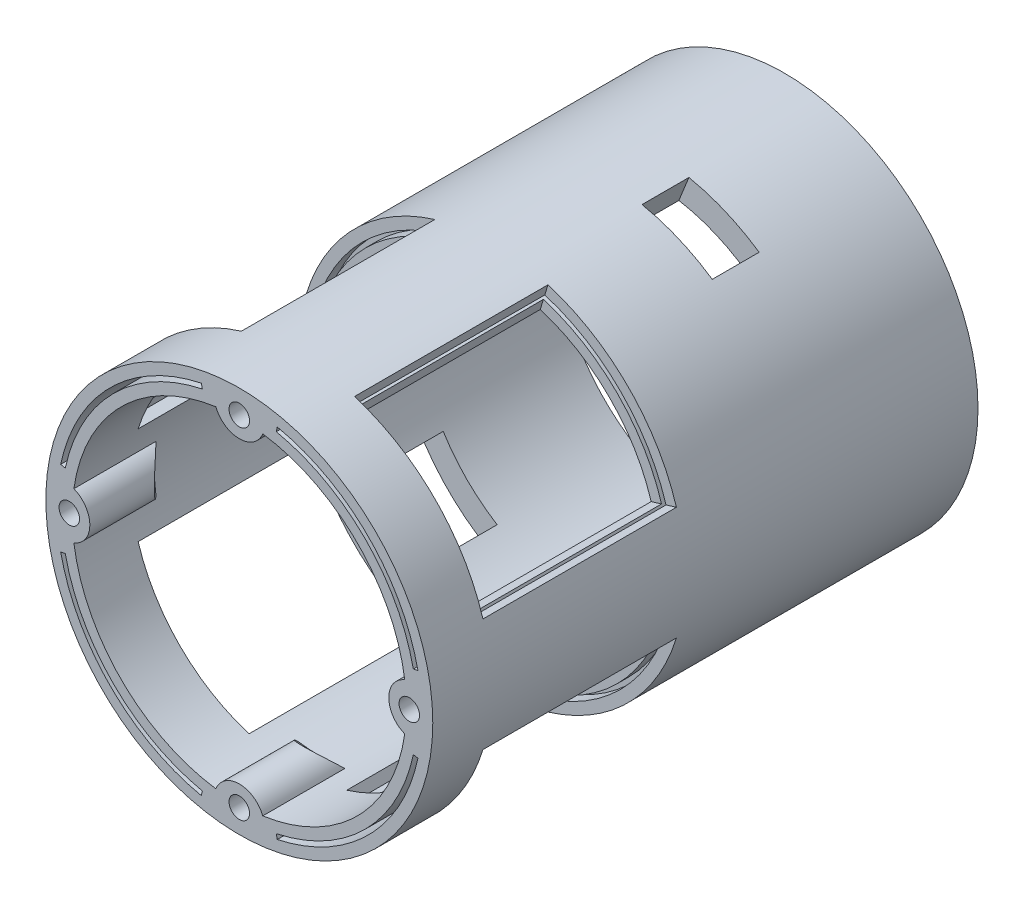
SolidWorks part; units mm, degrees
material "PEI"
ref_plane "Alzado" through (0, 0, 0) normal (0, 0, 1) x (1, 0, 0)
ref_plane "Planta" through (0, 0, 0) normal (0, 1, 0) x (1, 0, 0)
ref_plane "Vista lateral" through (0, 0, 0) normal (1, 0, 0) x (0, 0, -1)
sketch "Croquis1" plane through (0, 0, 0) normal (0, 0, 1) x (1, 0, 0)
  circle A0 centre (0, 0) radius 33
  circle A1 centre (0, 0) radius 28.5
  dimension "D1" = 66
  dimension "D2" = 4.5
extrude "Boss-Extrude1" add sketch "Croquis1" along normal blind 93
sketch "Croquis2" plane through (0, 0, 93) normal (0, 0, 1) x (1, 0, 0)
  line L0 (0, 0) -> (-6.4764, -30.4693) construction
  line L1 (0, 0) -> (-30.4693, -6.4764) construction
  line L2 (0, 0) -> (0, -30.5) construction
  line L3 (0, 0) -> (-30.5, 0) construction
  line L4 (-30.4693, -6.4764) -> (-29.6868, -6.3101)
  line L5 (-6.4764, -30.4693) -> (-6.3101, -29.6868)
  line L6 (-30.4693, 6.4764) -> (-29.6868, 6.3101)
  line L7 (-6.4764, 30.4693) -> (-6.3101, 29.6868)
  line L8 (6.4764, 30.4693) -> (6.3101, 29.6868)
  line L9 (30.4693, 6.4764) -> (29.6868, 6.3101)
  line L10 (30.4693, -6.4764) -> (29.6868, -6.3101)
  line L11 (6.4764, -30.4693) -> (6.3101, -29.6868)
  circle A0 centre (0, 0) radius 30.35 construction
  circle A1 centre (0, 0) radius 31.15 construction
  circle A2 centre (0, 0) radius 33 construction
  circle A3 centre (0, 0) radius 30.75 construction
  arc A4 (-6.4764, -30.4693) -> (-30.4693, -6.4764) centre (0, 0) cw
  arc A5 (-6.3101, -29.6868) -> (-29.6868, -6.3101) centre (0, 0) cw
  arc A6 (-30.4693, 6.4764) -> (-6.4764, 30.4693) centre (0, 0) cw
  arc A7 (-29.6868, 6.3101) -> (-6.3101, 29.6868) centre (0, 0) cw
  arc A8 (6.4764, 30.4693) -> (30.4693, 6.4764) centre (0, 0) cw
  arc A9 (6.3101, 29.6868) -> (29.6868, 6.3101) centre (0, 0) cw
  arc A10 (30.4693, -6.4764) -> (6.4764, -30.4693) centre (0, 0) cw
  arc A11 (29.6868, -6.3101) -> (6.3101, -29.6868) centre (0, 0) cw
  circle A12 centre (0, 0) radius 28.5 construction
  point P4 (-6.3933, -30.078)
  point P32 (0, 0)
  dimension "D3" = 12
  dimension "D4" = 12
  dimension "D1" = 0.8
  dimension "D2" = 4.5
  dimension "D6" = 2.25
  dimension "D5" = 4
extrude "Cortar-Extruir1" cut sketch "Croquis2" against normal blind 45
ref_axis "Eje1" through (0, 0, 93) along (0, 0, -1)
ref_plane "Plano2" through (0, 0, 0) normal (0.9563, -0.2924, 0) x (0, 0, -1)
sketch "Croquis4" plane through (0, 0, 0) normal (0.9563, -0.2924, 0) x (0, 0, -1)
  line L0 (-83, 33) -> (-83, 28.266)
  line L1 (0, 33) -> (-93, 33) construction
  line L2 (-83, 28.266) -> (-50, 28.266)
  line L4 (-50, 33) -> (-83, 33)
  line L5 (-97, 29) -> (-42, 29) construction
  line L6 (-93, 33) -> (-93, -33) construction
  line L14 (-50, 28.266) -> (-50, 33)
  point P10 (-83, 28.1943)
  point P11 (-49.9679, 28.266)
  dimension "D1" = 4.734
  dimension "D6" = 10
revolve "Cortar-Revolución2" cut sketch "Croquis4" angle 56 about axis through (0, 0, 93) along (0, 0, -1)
pattern_circular "MatrizC2" count 4 over 360 about axis through (0, 0, 93) along (0, 0, -1) of "Cortar-Revolución2"
sketch "Sketch8" plane through (0, 0, 0) normal (0, 0, -1) x (-1, 0, 0)
  arc A0 (-4, -28.2179) -> (4, -28.2179) centre (0, 0) ccw
  circle A1 centre (0, 0) radius 28.5 construction
  arc A2 (-4, -28.2179) -> (4, -28.2179) centre (0, -29.7959) cw
  arc A3 (-28.2179, 4) -> (-28.2179, -4) centre (0, 0) ccw
  arc A4 (-28.2179, 4) -> (-28.2179, -4) centre (-29.7959, 0) cw
  arc A5 (4, 28.2179) -> (-4, 28.2179) centre (0, 0) ccw
  arc A6 (4, 28.2179) -> (-4, 28.2179) centre (0, 29.7959) cw
  arc A7 (28.2179, -4) -> (28.2179, 4) centre (0, 0) ccw
  arc A8 (28.2179, -4) -> (28.2179, 4) centre (29.7959, 0) cw
  point P8 (0, -25.4959)
  point P20 (0, 0)
  dimension "D1" = 4.3
  dimension "D2" = 8
  dimension "D3" = 4
extrude "Boss-Extrude4" add sketch "Sketch8" against normal blind 11
sketch "Sketch9" plane through (0, 0, 0) normal (0, 0, -1) x (-1, 0, 0)
  circle A0 centre (0, -29) radius 1.75
  circle A1 centre (0, 0) radius 29 construction
  circle A2 centre (0, 0) radius 33 construction
  circle A3 centre (-29, 0) radius 1.75
  circle A4 centre (0, 29) radius 1.75
  circle A5 centre (29, 0) radius 1.75
  point P16 (0, 0)
  dimension "D1" = 4
  dimension "D2" = 3.5
  dimension "D3" = 4
extrude "Cut-Extrude3" cut sketch "Sketch9" against normal blind 10
ref_plane "Mid plane" through (0, 0, 46.5) normal (0, 0, 1) x (1, 0, 0)
mirror "Mirror1" about plane through (0, 0, 46.5) normal (0, 0, 1) of "Cut-Extrude3", "Boss-Extrude4"
ref_plane "Plano para USB y Switch" through (-23.3345, -23.3345, 0) normal (-0.7071, -0.7071, 0) x (0, 0, -1)
sketch "Sketch10" plane through (-23.3345, -23.3345, 0) normal (-0.7071, -0.7071, 0) x (0, 0, -1)
  line L0 (0, -33) -> (0, 33) construction
  line L1 (-10.5, 7.5) -> (-3.5, 7.5)
  line L2 (-10.5, 7.5) -> (-10.5, -7.5)
  line L3 (-10.5, -7.5) -> (-3.5, -7.5)
  line L4 (-3.5, 7.5) -> (-3.5, -7.5)
  line L5 (-10.5, 7.5) -> (-3.5, -7.5) construction
  line L6 (-10.5, -7.5) -> (-3.5, 7.5) construction
  line L8 (-42, 6.5) -> (-34, 6.5)
  line L9 (-42, 6.5) -> (-42, -6.5)
  line L10 (-42, -6.5) -> (-34, -6.5)
  line L11 (-34, 6.5) -> (-34, -6.5)
  line L12 (-42, 6.5) -> (-34, -6.5) construction
  line L13 (-42, -6.5) -> (-34, 6.5) construction
  point P0 (-7, 0)
  point P9 (-38, 0)
  dimension "D1" = 7
  dimension "D2" = 15
  dimension "D3" = 7
  dimension "D4" = 13
  dimension "D5" = 8
  dimension "D6" = 38
extrude "Corte USB y Switch" cut sketch "Sketch10" against normal blind 10
ref_plane "Plano USB PCB_C" through (12.362, 30.5971, 0) normal (0.3746, 0.9272, 0) x (0, 0, -1)
sketch "Sketch11" plane through (12.362, 30.5971, 0) normal (0.3746, 0.9272, 0) x (0, 0, -1)
  line L0 (0, -33) -> (0, 33) construction
  line L1 (-30.9, 6) -> (-22.9, 6)
  line L2 (-30.9, 6) -> (-30.9, -7)
  line L3 (-30.9, -7) -> (-22.9, -7)
  line L4 (-22.9, 6) -> (-22.9, -7)
  line L5 (-30.9, 6) -> (-22.9, -7) construction
  line L6 (-30.9, -7) -> (-22.9, 6) construction
  point P0 (-26.9, -0.5)
  dimension "D1" = 0.5
  dimension "D2" = 8
  dimension "D3" = 13
  dimension "D4" = 22.9
extrude "Cut-Extrude5" cut sketch "Sketch11" against normal blind 10
chamfer "Chamfer1" distance 3 angle 45 4 edges at (0, 28.5, 82) (-28.5, 0, 82) (28.5, 0, 82) (0, -28.5, 82)
equation "\"D6@Croquis2\"=\"D2@Croquis2\"/2"
